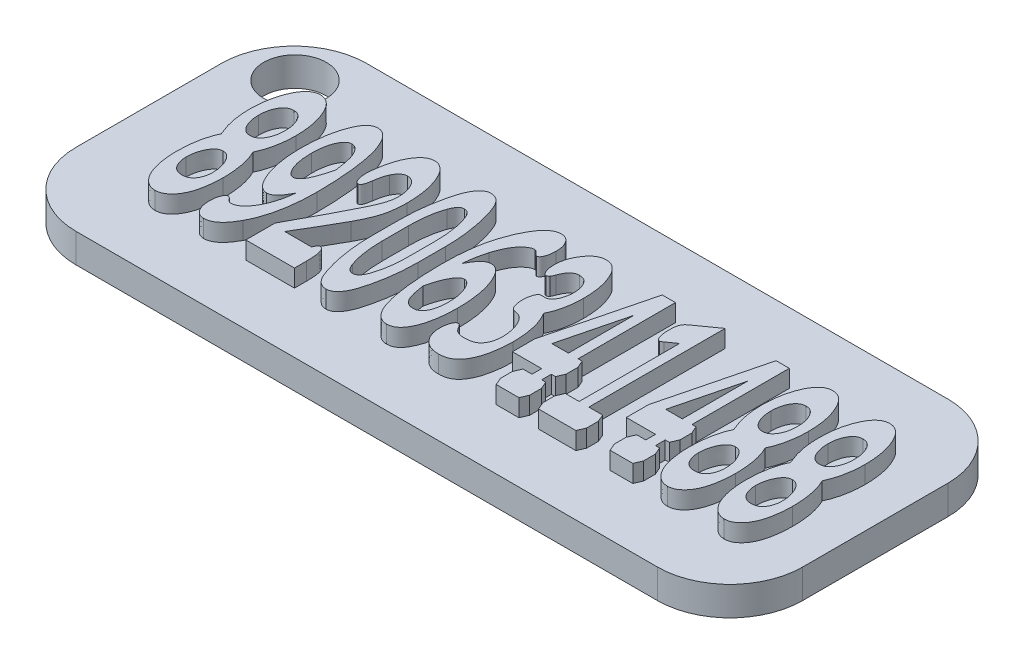
SolidWorks part; units mm, degrees
ref_plane "Спереди" through (0, 0, 0) normal (0, 0, 1) x (1, 0, 0)
ref_plane "Сверху" through (0, 0, 0) normal (0, 1, 0) x (1, 0, 0)
ref_plane "Справа" through (0, 0, 0) normal (1, 0, 0) x (0, 0, -1)
other "Configuration Table"
sketch "Эскиз1" plane through (0, 0, 0) normal (0, 1, 0) x (1, 0, 0)
  line L1 (0, 0) -> (50, 0)
  line L2 (0, 0) -> (0, 20)
  line L3 (0, 20) -> (50, 20)
  line L4 (50, 0) -> (50, 20)
  dimension "D1" = 20
  dimension "D2" = 50
extrude "Бобышка-Вытянуть1" add sketch "Эскиз1" along normal blind 2 contours L2 L3 L4 L1
sketch "Эскиз2" plane through (0, 2, 0) normal (0, 1, 0) x (1, 0, 0)
  line L0 (-2.8341, 4.1295) -> (51.2146, 4.1295) construction
  text T0 "<b> 89206341488</b>" font "Courier New" height in points 48
extrude "номер" add sketch "Эскиз2" along normal blind 1.2
fillet "Скругление1" radius 5 1 edges at (0, 1, -20)
fillet "Скругление2" radius 5 1 edges at (0, 1, 0)
fillet "Скругление3" radius 5 1 edges at (50, 1, -20)
fillet "Скругление4" radius 5 1 edges at (50, 1, 0)
sketch "Эскиз4" plane through (0, 2, 0) normal (0, 1, 0) x (1, 0, 0)
  circle A0 centre (3.5425, 16.5284) radius 2.1519
extrude "Вырез-Вытянуть1" cut sketch "Эскиз4" against normal blind 3
